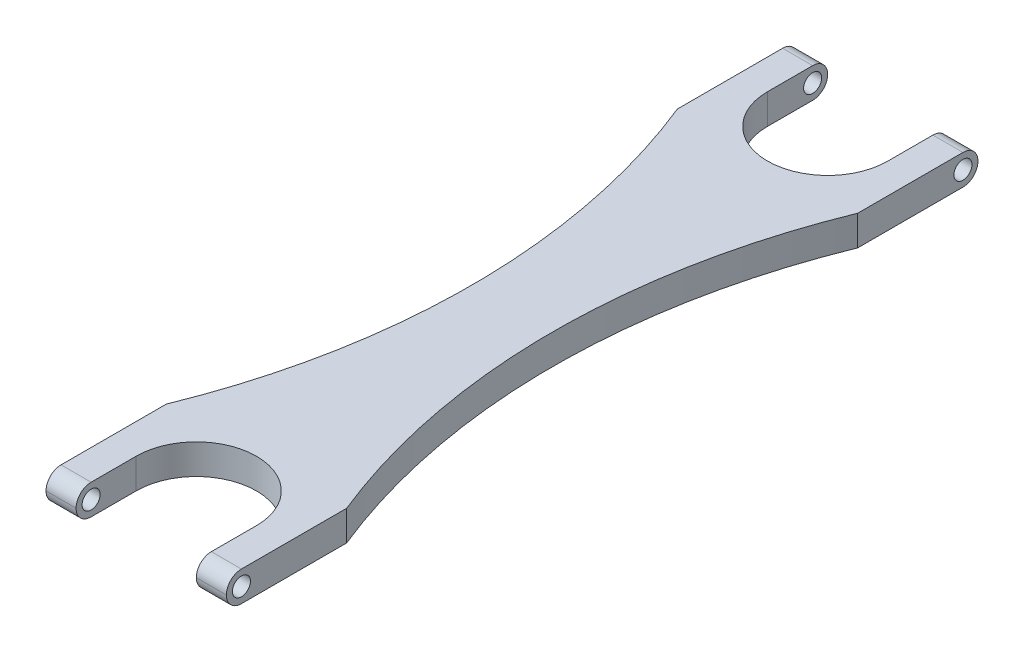
SolidWorks part; units mm, degrees
ref_plane "Front Plane" through (0, 0, 0) normal (0, 0, 1) x (1, 0, 0)
ref_plane "Top Plane" through (0, 0, 0) normal (0, 1, 0) x (1, 0, 0)
ref_plane "Right Plane" through (0, 0, 0) normal (1, 0, 0) x (0, 0, -1)
sketch "Sketch1" plane through (0, 0, 0) normal (0, 1, 0) x (1, 0, 0)
  line L0 (0, 0) -> (12.7, 0)
  line L1 (12.7, 0) -> (12.7, -25.4)
  line L2 (0, 0) -> (0, -50.8)
  line L3 (0, -266.7) -> (0, -317.5)
  line L4 (0, -317.5) -> (12.7, -317.5)
  line L5 (12.7, -317.5) -> (12.7, -292.1)
  line L6 (38.1, -50.8) -> (38.1, -266.7) construction
  line L7 (63.5, -317.5) -> (63.5, -292.1)
  line L8 (76.2, -317.5) -> (63.5, -317.5)
  line L9 (76.2, -266.7) -> (76.2, -317.5)
  line L10 (76.2, 0) -> (76.2, -50.8)
  line L11 (63.5, 0) -> (63.5, -25.4)
  line L12 (76.2, 0) -> (63.5, 0)
  arc A0 (12.7, -25.4) -> (38.1, -50.8) centre (38.1, -25.4) ccw
  arc A1 (0, -50.8) -> (0, -266.7) centre (-266.7, -158.75) cw
  arc A2 (12.7, -292.1) -> (38.1, -266.7) centre (38.1, -292.1) cw
  arc A3 (63.5, -292.1) -> (38.1, -266.7) centre (38.1, -292.1) ccw
  arc A4 (63.5, -25.4) -> (38.1, -50.8) centre (38.1, -25.4) cw
  arc A5 (76.2, -50.8) -> (76.2, -266.7) centre (342.9, -158.75) ccw
  dimension "D8" = 609.6
  dimension "D1" = 317.5
  dimension "D2" = 12.7
  dimension "D3" = 50.8
  dimension "D4" = 25.4
  dimension "D5" = 25.4
  dimension "D6" = 50.8
  dimension "D7" = 50.8
extrude "Boss-Extrude1" add sketch "Sketch1" along normal blind 12.7
fillet "Fillet1" radius 6.35 8 edges at (69.85, 0, 0) (6.35, 0, 0) (69.85, 12.7, 0) (6.35, 12.7, 0) (6.35, 0, 317.5) (6.35, 12.7, 317.5) (69.85, 0, 317.5) (69.85, 12.7, 317.5)
sketch "Sketch2" plane through (76.2, 0, 0) normal (1, 0, 0) x (0, 0, -1)
  circle A0 centre (-311.15, 6.35) radius 3.81
extrude "Cut-Extrude1" cut sketch "Sketch2" against normal through all
sketch "Sketch3" plane through (76.2, 0, 0) normal (1, 0, 0) x (0, 0, -1)
  circle A0 centre (-6.35, 6.35) radius 3.81
extrude "Cut-Extrude2" cut sketch "Sketch3" against normal through all
